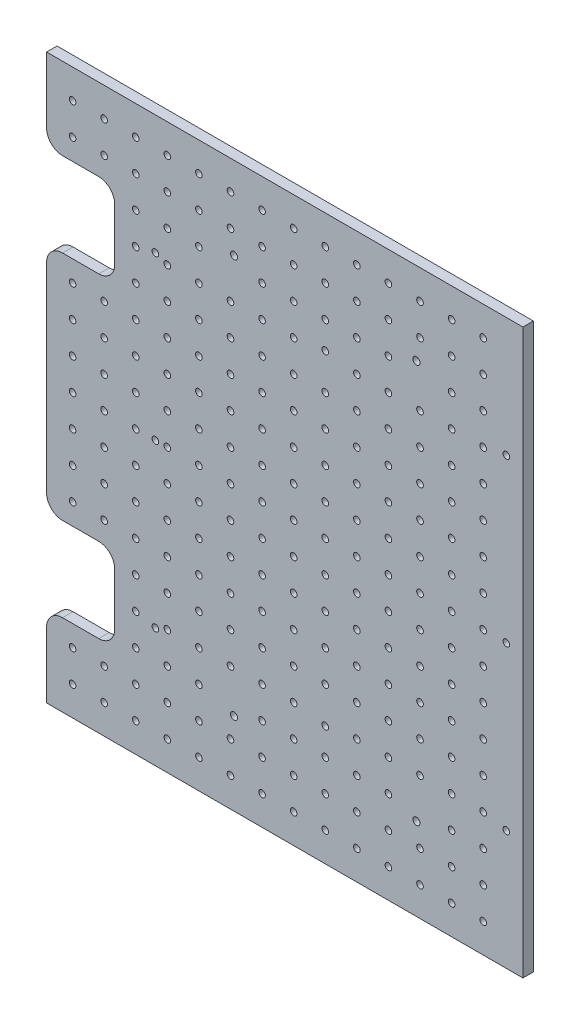
SolidWorks part; units mm, degrees
ref_plane "Front Plane" through (0, 0, 0) normal (0, 0, 1) x (1, 0, 0)
ref_plane "Top Plane" through (0, 0, 0) normal (0, 1, 0) x (1, 0, 0)
ref_plane "Right Plane" through (0, 0, 0) normal (1, 0, 0) x (0, 0, -1)
sketch "Sketch1" plane through (0, 0, 0) normal (0, 0, 1) x (1, 0, 0)
  line L1 (-143.635, 170) -> (143.635, 170)
  line L2 (-143.635, 170) -> (-143.635, -170)
  line L3 (-143.635, -170) -> (143.635, -170)
  line L4 (143.635, 170) -> (143.635, -170)
  dimension "D1" = 287.27
  dimension "D2" = 340
  dimension "D3" = 170
  dimension "D4" = 143.635
extrude "Base_Plate-Extrude" add sketch "Sketch1" along normal blind 6.3
sketch "Sketch3" plane through (0, 0, 6.3) normal (0, 0, 1) x (1, 0, 0)
  line L0 (218.6774, 98) -> (-212.5391, 98) construction
  line L1 (218.7113, -98) -> (-212.5283, -98) construction
  line L2 (133.635, 226.7998) -> (133.635, -231.3038) construction
  line L3 (143.635, -170) -> (143.635, 170) construction
  line L4 (-78.025, 174.4237) -> (-78.025, -178.7911) construction
  line L5 (412.3614, 0) -> (1049.4297, 0) construction
  line L6 (79.415, 225.6084) -> (79.415, -232.4952) construction
  line L7 (-30.585, -232.4952) -> (-30.585, 225.6084) construction
  line L8 (95.7553, 120.25) -> (-187.2723, 120.25) construction
  line L9 (88.1602, -120.25) -> (-163.8184, -120.25) construction
  circle A0 centre (133.635, 98) radius 2
  circle A1 centre (24.415, 98) radius 2
  circle A2 centre (-78.025, 98) radius 2
  circle A3 centre (-78.025, -98) radius 2
  circle A4 centre (24.415, -98) radius 2
  circle A5 centre (133.635, -98) radius 2
  circle A8 centre (133.635, 0) radius 2
  circle A9 centre (-78.025, 0) radius 2
  circle A85 centre (79.415, -120.25) radius 2.15
  circle A86 centre (-30.585, -120.25) radius 2.15
  circle A87 centre (-30.585, 120.25) radius 2.15
  circle A88 centre (79.415, 120.25) radius 2.15
  point P45 (0, 0)
  dimension "D1" = 4
  dimension "D8" = 4
  dimension "D9" = 4
  dimension "D10" = 4
  dimension "D11" = 4
  dimension "D12" = 4
  dimension "D16" = 4
  dimension "D17" = 4
  dimension "D20" = 4.3
  dimension "D21" = 4.3
  dimension "D22" = 4.3
  dimension "D23" = 4.3
  dimension "D3" = 109.22
  dimension "D4" = 102.44
  dimension "D5" = 102.44
  dimension "D6" = 109.22
  dimension "D2" = 196
  dimension "D7" = 98
  dimension "D13" = 10
  dimension "D14" = 98
  dimension "D15" = 98
  dimension "D18" = 110
  dimension "D19" = 240.5
  dimension "D24" = 120.25
  dimension "D25" = 55
extrude "Plate_to_Plate_Mnt-Thru-Hole" cut sketch "Sketch3" against normal through all
sketch "Sketch4" plane through (0, 0, 6.3) normal (0, 0, 1) x (1, 0, 0)
  line L0 (283.705, 0) -> (-313.8392, 0) construction
  line L1 (143.635, -170) -> (143.635, 170) construction
  circle A0 centre (-70.835, 0) radius 2
  circle A1 centre (-78.025, 0) radius 2 construction
  circle A2 centre (-51.785, 0) radius 2
  circle A3 centre (-32.735, 0) radius 2
  circle A4 centre (-13.685, 0) radius 2
  circle A5 centre (5.365, 0) radius 2
  circle A6 centre (24.415, 0) radius 2
  circle A7 centre (43.465, 0) radius 2
  circle A8 centre (62.515, 0) radius 2
  circle A9 centre (81.565, 0) radius 2
  circle A10 centre (100.615, 0) radius 2
  circle A11 centre (119.665, 0) radius 2
  circle A12 centre (-70.835, 19.05) radius 2
  circle A13 centre (-51.785, 19.05) radius 2
  circle A14 centre (-32.735, 19.05) radius 2
  circle A15 centre (-13.685, 19.05) radius 2
  circle A16 centre (5.365, 19.05) radius 2
  circle A17 centre (24.415, 19.05) radius 2
  circle A18 centre (43.465, 19.05) radius 2
  circle A19 centre (62.515, 19.05) radius 2
  circle A20 centre (81.565, 19.05) radius 2
  circle A21 centre (100.615, 19.05) radius 2
  circle A22 centre (119.665, 19.05) radius 2
  circle A23 centre (-70.835, 38.1) radius 2
  circle A24 centre (-51.785, 38.1) radius 2
  circle A25 centre (-32.735, 38.1) radius 2
  circle A26 centre (-13.685, 38.1) radius 2
  circle A27 centre (5.365, 38.1) radius 2
  circle A28 centre (24.415, 38.1) radius 2
  circle A29 centre (43.465, 38.1) radius 2
  circle A30 centre (62.515, 38.1) radius 2
  circle A31 centre (81.565, 38.1) radius 2
  circle A32 centre (100.615, 38.1) radius 2
  circle A33 centre (119.665, 38.1) radius 2
  circle A34 centre (-70.835, 57.15) radius 2
  circle A35 centre (-51.785, 57.15) radius 2
  circle A36 centre (-32.735, 57.15) radius 2
  circle A37 centre (-13.685, 57.15) radius 2
  circle A38 centre (5.365, 57.15) radius 2
  circle A39 centre (24.415, 57.15) radius 2
  circle A40 centre (43.465, 57.15) radius 2
  circle A41 centre (62.515, 57.15) radius 2
  circle A42 centre (81.565, 57.15) radius 2
  circle A43 centre (100.615, 57.15) radius 2
  circle A44 centre (119.665, 57.15) radius 2
  circle A45 centre (-70.835, -19.05) radius 2
  circle A46 centre (-51.785, -19.05) radius 2
  circle A47 centre (-32.735, -19.05) radius 2
  circle A48 centre (-13.685, -19.05) radius 2
  circle A49 centre (5.365, -19.05) radius 2
  circle A50 centre (24.415, -19.05) radius 2
  circle A51 centre (43.465, -19.05) radius 2
  circle A52 centre (62.515, -19.05) radius 2
  circle A53 centre (81.565, -19.05) radius 2
  circle A54 centre (100.615, -19.05) radius 2
  circle A55 centre (119.665, -19.05) radius 2
  circle A56 centre (-70.835, -38.1) radius 2
  circle A57 centre (-51.785, -38.1) radius 2
  circle A58 centre (-32.735, -38.1) radius 2
  circle A59 centre (-13.685, -38.1) radius 2
  circle A60 centre (5.365, -38.1) radius 2
  circle A61 centre (24.415, -38.1) radius 2
  circle A62 centre (43.465, -38.1) radius 2
  circle A63 centre (62.515, -38.1) radius 2
  circle A64 centre (81.565, -38.1) radius 2
  circle A65 centre (100.615, -38.1) radius 2
  circle A66 centre (119.665, -38.1) radius 2
  circle A67 centre (-70.835, -57.15) radius 2
  circle A68 centre (-51.785, -57.15) radius 2
  circle A69 centre (-32.735, -57.15) radius 2
  circle A70 centre (-13.685, -57.15) radius 2
  circle A71 centre (5.365, -57.15) radius 2
  circle A72 centre (24.415, -57.15) radius 2
  circle A73 centre (43.465, -57.15) radius 2
  circle A74 centre (62.515, -57.15) radius 2
  circle A75 centre (81.565, -57.15) radius 2
  circle A76 centre (100.615, -57.15) radius 2
  circle A77 centre (119.665, -57.15) radius 2
  circle A78 centre (133.635, 0) radius 2 construction
  dimension "D1" = 7.19
  dimension "D2" = 4
  dimension "D4" = 11
  dimension "D3" = 4
  dimension "D5" = 4
extrude "Center_Perforation-Thru-Hole" cut sketch "Sketch4" against normal through all
sketch "Sketch6" plane through (0, 0, 6.3) normal (0, 0, 1) x (1, 0, 0)
  line L0 (-34.6497, 0) -> (-186.3903, 0) construction
  line L1 (81.565, -183.8925) -> (81.565, 197.7612) construction
  line L2 (119.665, -208.9594) -> (119.665, 225.074) construction
  line L3 (-70.835, -206.2107) -> (-70.835, 262.0393) construction
  line L4 (-32.735, 186.3499) -> (-32.735, -192.7852) construction
  circle A0 centre (-89.885, 0) radius 2
  circle A1 centre (-51.785, -95.25) radius 2
  circle A2 centre (-70.835, 0) radius 2 construction
  circle A3 centre (-70.835, -95.25) radius 2
  circle A4 centre (-108.935, 0) radius 2
  circle A5 centre (-127.985, 0) radius 2
  circle A6 centre (-89.885, 19.05) radius 2
  circle A7 centre (-108.935, 19.05) radius 2
  circle A8 centre (-127.985, 19.05) radius 2
  circle A9 centre (-89.885, 38.1) radius 2
  circle A10 centre (-108.935, 38.1) radius 2
  circle A11 centre (-127.985, 38.1) radius 2
  circle A12 centre (-89.885, 57.15) radius 2
  circle A13 centre (-108.935, 57.15) radius 2
  circle A14 centre (-127.985, 57.15) radius 2
  circle A15 centre (-89.885, 76.2) radius 2
  circle A16 centre (-108.935, 76.2) radius 2
  circle A17 centre (-127.985, 76.2) radius 2
  circle A18 centre (-89.885, 95.25) radius 2
  circle A19 centre (-108.935, 95.25) radius 2
  circle A20 centre (-127.985, 95.25) radius 2
  circle A21 centre (-89.885, 114.3) radius 2
  circle A22 centre (-108.935, 114.3) radius 2
  circle A23 centre (-127.985, 114.3) radius 2
  circle A24 centre (-89.885, 133.35) radius 2
  circle A25 centre (-108.935, 133.35) radius 2
  circle A26 centre (-127.985, 133.35) radius 2
  circle A27 centre (-89.885, 152.4) radius 2
  circle A28 centre (-108.935, 152.4) radius 2
  circle A29 centre (-127.985, 152.4) radius 2
  circle A30 centre (-89.885, -19.05) radius 2
  circle A31 centre (-108.935, -19.05) radius 2
  circle A32 centre (-127.985, -19.05) radius 2
  circle A33 centre (-89.885, -38.1) radius 2
  circle A34 centre (-108.935, -38.1) radius 2
  circle A35 centre (-127.985, -38.1) radius 2
  circle A36 centre (-89.885, -57.15) radius 2
  circle A37 centre (-108.935, -57.15) radius 2
  circle A38 centre (-127.985, -57.15) radius 2
  circle A39 centre (-89.885, -76.2) radius 2
  circle A40 centre (-108.935, -76.2) radius 2
  circle A41 centre (-127.985, -76.2) radius 2
  circle A42 centre (-89.885, -95.25) radius 2
  circle A43 centre (-108.935, -95.25) radius 2
  circle A44 centre (-127.985, -95.25) radius 2
  circle A45 centre (-89.885, -114.3) radius 2
  circle A46 centre (-108.935, -114.3) radius 2
  circle A47 centre (-127.985, -114.3) radius 2
  circle A48 centre (-89.885, -133.35) radius 2
  circle A49 centre (-108.935, -133.35) radius 2
  circle A50 centre (-127.985, -133.35) radius 2
  circle A51 centre (-89.885, -152.4) radius 2
  circle A52 centre (-108.935, -152.4) radius 2
  circle A53 centre (-127.985, -152.4) radius 2
  circle A54 centre (-51.785, -114.3) radius 2
  circle A55 centre (-70.835, -114.3) radius 2
  circle A56 centre (119.665, -76.2) radius 2
  circle A57 centre (100.615, -76.2) radius 2
  circle A58 centre (119.665, -57.15) radius 2 construction
  circle A59 centre (100.615, -57.15) radius 2 construction
  circle A60 centre (119.665, -95.25) radius 2
  circle A61 centre (100.615, -95.25) radius 2
  circle A62 centre (119.665, -114.3) radius 2
  circle A63 centre (100.615, -114.3) radius 2
  circle A64 centre (119.665, -133.35) radius 2
  circle A65 centre (100.615, -133.35) radius 2
  circle A66 centre (119.665, -152.4) radius 2
  circle A67 centre (100.615, -152.4) radius 2
  circle A68 centre (-51.785, -133.35) radius 2
  circle A69 centre (119.665, 76.2) radius 2
  circle A70 centre (100.615, 76.2) radius 2
  circle A71 centre (100.615, 57.15) radius 2 construction
  circle A72 centre (119.665, 57.15) radius 2 construction
  circle A73 centre (119.665, 95.25) radius 2
  circle A74 centre (100.615, 95.25) radius 2
  circle A75 centre (119.665, 114.3) radius 2
  circle A76 centre (100.615, 114.3) radius 2
  circle A77 centre (119.665, 133.35) radius 2
  circle A78 centre (100.615, 133.35) radius 2
  circle A79 centre (119.665, 152.4) radius 2
  circle A80 centre (100.615, 152.4) radius 2
  circle A81 centre (-70.835, 76.2) radius 2
  circle A82 centre (-51.785, 76.2) radius 2
  circle A83 centre (-70.835, -76.2) radius 2
  circle A84 centre (-51.785, -76.2) radius 2
  circle A85 centre (-70.835, 57.15) radius 2 construction
  circle A86 centre (-51.785, 57.15) radius 2 construction
  circle A87 centre (-70.835, -57.15) radius 2 construction
  circle A88 centre (-51.785, -57.15) radius 2 construction
  circle A89 centre (-51.785, 95.25) radius 2
  circle A90 centre (-70.835, 95.25) radius 2
  circle A91 centre (-51.785, 114.3) radius 2
  circle A92 centre (-70.835, 114.3) radius 2
  circle A93 centre (-51.785, 133.35) radius 2
  circle A94 centre (-70.835, 133.35) radius 2
  circle A95 centre (-51.785, 152.4) radius 2
  circle A96 centre (-70.835, 152.4) radius 2
  circle A97 centre (-70.835, -133.35) radius 2
  circle A98 centre (-51.785, -152.4) radius 2
  circle A99 centre (-70.835, -152.4) radius 2
  circle A100 centre (62.515, -152.4) radius 2
  circle A101 centre (81.565, -76.2) radius 2
  circle A103 centre (81.565, -152.4) radius 2
  circle A105 centre (81.565, 76.2) radius 2
  circle A107 centre (81.565, 152.4) radius 2
  circle A108 centre (81.565, 57.15) radius 2 construction
  circle A109 centre (62.515, -76.2) radius 2
  circle A110 centre (62.515, 76.2) radius 2
  circle A111 centre (62.515, 152.4) radius 2
  circle A112 centre (43.465, -152.4) radius 2
  circle A113 centre (43.465, -76.2) radius 2
  circle A114 centre (43.465, 76.2) radius 2
  circle A115 centre (43.465, 152.4) radius 2
  circle A116 centre (24.415, -152.4) radius 2
  circle A117 centre (24.415, -76.2) radius 2
  circle A118 centre (24.415, 76.2) radius 2
  circle A119 centre (24.415, 152.4) radius 2
  circle A120 centre (5.365, -152.4) radius 2
  circle A121 centre (5.365, -76.2) radius 2
  circle A122 centre (5.365, 76.2) radius 2
  circle A123 centre (5.365, 152.4) radius 2
  circle A124 centre (-13.685, -152.4) radius 2
  circle A125 centre (-13.685, -76.2) radius 2
  circle A126 centre (-13.685, 76.2) radius 2
  circle A127 centre (-13.685, 152.4) radius 2
  circle A128 centre (-32.735, -152.4) radius 2
  circle A129 centre (-32.735, -76.2) radius 2
  circle A130 centre (-32.735, 76.2) radius 2
  circle A131 centre (-32.735, 152.4) radius 2
  circle A132 centre (-51.785, -152.4) radius 2
  circle A133 centre (-51.785, -76.2) radius 2
  circle A134 centre (-51.785, 76.2) radius 2
  circle A135 centre (-51.785, 152.4) radius 2
  circle A136 centre (-70.835, -152.4) radius 2
  circle A137 centre (-70.835, -76.2) radius 2
  circle A138 centre (-70.835, 76.2) radius 2
  circle A139 centre (-70.835, 152.4) radius 2
  circle A140 centre (-89.885, -152.4) radius 2
  circle A141 centre (-89.885, -76.2) radius 2
  circle A142 centre (-89.885, 76.2) radius 2
  circle A143 centre (-89.885, 152.4) radius 2
  circle A144 centre (81.565, -133.35) radius 2
  circle A145 centre (-32.735, -133.35) radius 2
  circle A146 centre (5.365, -95.25) radius 2
  circle A147 centre (-13.685, -95.25) radius 2
  circle A148 centre (-32.735, -95.25) radius 2
  circle A149 centre (81.565, -95.25) radius 2
  circle A150 centre (62.515, -95.25) radius 2
  circle A151 centre (43.465, -95.25) radius 2
  circle A156 centre (-32.735, 95.25) radius 2
  circle A157 centre (-13.685, 95.25) radius 2
  circle A158 centre (5.365, 95.25) radius 2
  circle A159 centre (43.465, 95.25) radius 2
  circle A160 centre (62.515, 95.25) radius 2
  circle A161 centre (81.565, 95.25) radius 2
  circle A166 centre (62.515, 133.35) radius 2
  circle A167 centre (43.465, 133.35) radius 2
  circle A168 centre (24.415, 133.35) radius 2
  circle A169 centre (5.365, 133.35) radius 2
  circle A170 centre (-13.685, 133.35) radius 2
  circle A171 centre (62.515, 114.3) radius 2
  circle A172 centre (43.465, 114.3) radius 2
  circle A173 centre (24.415, 114.3) radius 2
  circle A174 centre (5.365, 114.3) radius 2
  circle A175 centre (-13.685, 114.3) radius 2
  circle A176 centre (62.515, -133.35) radius 2
  circle A177 centre (43.465, -133.35) radius 2
  circle A178 centre (24.415, -133.35) radius 2
  circle A179 centre (5.365, -133.35) radius 2
  circle A180 centre (-13.685, -133.35) radius 2
  circle A181 centre (62.515, -114.3) radius 2
  circle A182 centre (43.465, -114.3) radius 2
  circle A183 centre (24.415, -114.3) radius 2
  circle A184 centre (5.365, -114.3) radius 2
  circle A185 centre (-13.685, -114.3) radius 2
  circle A186 centre (81.565, 133.35) radius 2
  circle A187 centre (-32.735, 133.35) radius 2
  point P2 (-51.785, 0)
  point P3 (-70.835, 0)
  point P4 (81.565, -57.15)
  point P5 (-32.735, -57.15)
  point P6 (119.665, -57.15)
  point P166 (-70.835, -57.15)
  dimension "D1" = 4
  dimension "D2" = 19.05
  dimension "D3" = 3
  dimension "D4" = 9
  dimension "D6" = 19.05
  dimension "D7" = 19.05
  dimension "D8" = 19.05
  dimension "D9" = 4
  dimension "D10" = 4
  dimension "D12" = 19.05
  dimension "D13" = 19.05
  dimension "D14" = 19.05
  dimension "D15" = 4
  dimension "D16" = 4
  dimension "D18" = 19.05
  dimension "D19" = 19.05
  dimension "D20" = 19.05
  dimension "D21" = 19.05
  dimension "D22" = 19.05
  dimension "D23" = 19.05
  dimension "D24" = 4
  dimension "D25" = 4
  dimension "D26" = 4
  dimension "D27" = 4
  dimension "D30" = 19.05
  dimension "D31" = 76.2
  dimension "D32" = 76.2
  dimension "D33" = 4
  dimension "D34" = 10
  dimension "D35" = 4
  dimension "D36" = 19.05
  dimension "D37" = 19.05
  dimension "D38" = 4
  dimension "D39" = 4
  dimension "D40" = 4
  dimension "D41" = 4
  dimension "D42" = 19.05
  dimension "D47" = 4
  dimension "D48" = 19.05
  dimension "D49" = 4
  dimension "D50" = 19.05
  dimension "D5" = 9
  dimension "D11" = 5
  dimension "D17" = 5
  dimension "D28" = 5
  dimension "D29" = 5
  dimension "D43" = 2
  dimension "D45" = 2
  dimension "D44" = 3
  dimension "D46" = 3
extrude "Extended_Perforation-Thru-Hole" cut sketch "Sketch6" against normal through all
sketch "Sketch10" plane through (0, 0, 0) normal (0, 0, -1) x (-1, 0, 0)
  line L0 (-189.4299, 0) -> (209.3699, 0) construction
  line L1 (0, 228.4012) -> (0, -224.2923) construction
  line L2 (134.035, -69.85) -> (112.185, -69.85)
  line L3 (143.635, 170) -> (143.635, -170) construction
  line L4 (102.585, -79.45) -> (102.585, -111.05)
  line L5 (112.185, -120.65) -> (134.035, -120.65)
  line L7 (143.635, -130.25) -> (143.635, -162.3743) construction
  line L8 (143.635, -60.25) -> (143.635, -31.6818) construction
  line L9 (143.635, -130.25) -> (143.635, -60.25)
  line L10 (143.635, 60.25) -> (143.635, 31.6818) construction
  line L11 (143.635, 130.25) -> (143.635, 162.3743) construction
  line L12 (143.635, 130.25) -> (143.635, 60.25)
  line L13 (112.185, 120.65) -> (134.035, 120.65)
  line L14 (102.585, 79.45) -> (102.585, 111.05)
  line L15 (134.035, 69.85) -> (112.185, 69.85)
  circle A0 centre (108.935, -114.3) radius 2 construction
  circle A1 centre (108.935, -76.2) radius 2 construction
  circle A2 centre (108.935, -95.25) radius 2 construction
  arc A3 (112.185, -69.85) -> (102.585, -79.45) centre (112.185, -79.45) ccw
  arc A4 (102.585, -111.05) -> (112.185, -120.65) centre (112.185, -111.05) ccw
  arc A5 (134.035, -120.65) -> (143.635, -130.25) centre (134.035, -130.25) cw
  arc A6 (134.035, -69.85) -> (143.635, -60.25) centre (134.035, -60.25) ccw
  arc A7 (134.035, 69.85) -> (143.635, 60.25) centre (134.035, 60.25) cw
  arc A8 (134.035, 120.65) -> (143.635, 130.25) centre (134.035, 130.25) ccw
  arc A9 (102.585, 111.05) -> (112.185, 120.65) centre (112.185, 111.05) cw
  arc A10 (112.185, 69.85) -> (102.585, 79.45) centre (112.185, 79.45) cw
  point P26 (143.635, -120.65)
  point P29 (143.635, -69.85)
  point P43 (143.635, 69.85)
  point P44 (143.635, 120.65)
  dimension "D4" = 9.6
  dimension "D5" = 9.6
  dimension "D1" = 6.35
  dimension "D2" = 6.35
  dimension "D3" = 6.35
extrude "Cable_Routing-Cutout" cut sketch "Sketch10" against normal through all
equation "\"D3@Sketch1\"=\"D2@Sketch1\"/2"
equation "\"D4@Sketch1\"=\"D1@Sketch1\"/2"
equation "\"PLATE_LEN\"= 287.27"
equation "\"D1@Sketch1\"=\"PLATE_LEN\""
equation "\"PLATE_WID\"= 340"
equation "\"D2@Sketch1\"=\"PLATE_WID\""
equation "\"PLATE_THICKNESS\"=6.3"
equation "\"D1@Base_Plate-Extrude\" = \"PLATE_THICKNESS\""
equation "\"FRONT_TO_TRIPOD\"=110"
equation "\"TRIPOD_STRIDE\"=340"
equation "\"D7@Sketch3\"=\"D2@Sketch3\"/2"
equation "\"D14@Sketch3\"=\"D2@Sketch3\"/2"
equation "\"D15@Sketch3\"=\"D2@Sketch3\"/2"
equation "\"D24@Sketch3\"=\"D19@Sketch3\"/2"
equation "\"D25@Sketch3\"=\"D18@Sketch3\"/2"
equation "\"D1@Sketch10\"=19.05/3"
equation "\"D2@Sketch10\"=19.05/3"
equation "\"D3@Sketch10\"=19.05/3"
